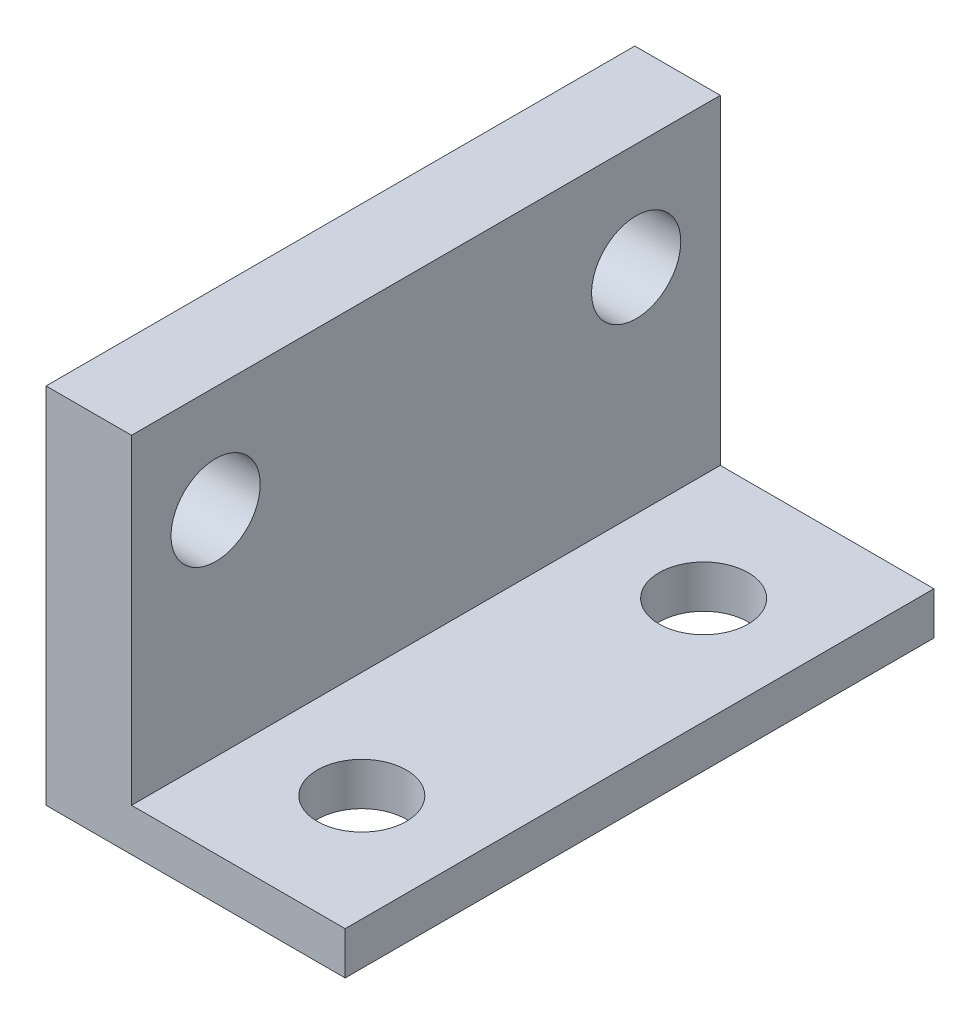
SolidWorks part; units mm, degrees
ref_plane "Front Plane" through (0, 0, 0) normal (0, 0, 1) x (1, 0, 0)
ref_plane "Top Plane" through (0, 0, 0) normal (0, 1, 0) x (1, 0, 0)
ref_plane "Right Plane" through (0, 0, 0) normal (1, 0, 0) x (0, 0, -1)
sketch "Sketch1" plane through (0, 0, 0) normal (0, 0, 1) x (1, 0, 0)
  line L1 (0, 0) -> (17.78, 0)
  line L2 (0, 0) -> (0, 2.54)
  line L3 (0, 2.54) -> (17.78, 2.54)
  line L4 (17.78, 0) -> (17.78, 2.54)
  line L5 (0, 2.54) -> (5.08, 2.54)
  line L6 (0, 2.54) -> (0, 21.59)
  line L7 (0, 21.59) -> (5.08, 21.59)
  line L8 (5.08, 2.54) -> (5.08, 21.59)
  dimension "D1" = 5.08
  dimension "D2" = 12.7
  dimension "D3" = 19.05
  dimension "D4" = 2.54
extrude "Boss-Extrude1" add sketch "Sketch1" along normal blind 35 contours L6 L5 L8 L7 | L2 L1 L4 L3
hole_wizard "Ø5.0mm Dowel Hole1" positions "Sketch2" profile "Sketch3" hole size "Ø5.0" standard "ANSI Metric" end condition through all
sketch "Sketch2" plane through (5.08, 0, 0) normal (1, 0, 0) x (0, 0, -1)
  line L4 (-30, 15.24) -> (-5, 15.24) construction
  line L6 (-35, 0) -> (0, 0) construction
  point P0 (-30, 15.24)
  point P2 (-5, 15.24)
  point P19 (-17.5, 0)
  point P20 (-17.5, 15.24)
  dimension "D1" = 25
  dimension "D2" = 15.24
sketch "Sketch3" plane through (5.08, 15.24, 30) normal (0, 1, 0) x (0, 0, -1)
  line L0 (0, 0) -> (0, 5.08)
  line L1 (0, 5.08) -> (2.65, 5.08)
  line L2 (2.65, 5.08) -> (2.65, 0)
  line L5 (2.65, 0) -> (0, 0)
  line L11 (0, -6.35) -> (0, 107.95) construction
  dimension "Thru Hole Dia." = 5.3
  dimension "Thru Hole Depth" = 5.08
hole_wizard "Ø5.0mm Dowel Hole2" positions "Sketch4" profile "Sketch5" hole size "Ø5.0" standard "ANSI Metric" end condition through all
sketch "Sketch4" plane through (0, 2.54, 0) normal (0, 1, 0) x (1, 0, 0)
  line L2 (11.43, -7.34) -> (11.43, -27.66) construction
  line L3 (17.78, -35) -> (17.78, 0) construction
  line L6 (0, -35) -> (0, 0) construction
  point P0 (11.43, -27.66)
  point P2 (11.43, -7.34)
  point P11 (11.3672, -27.38)
  point P12 (11.493, -7.06)
  point P16 (17.78, -17.5)
  point P17 (11.43, -17.5)
  dimension "D1" = 20.32
  dimension "D2" = 11.43
sketch "Sketch5" plane through (11.43, 2.54, 27.66) normal (1, 0, 0) x (0, 0, 1)
  line L0 (0, 0) -> (0, 2.54)
  line L1 (0, 2.54) -> (2.65, 2.54)
  line L2 (2.65, 2.54) -> (2.65, 0)
  line L5 (2.65, 0) -> (0, 0)
  line L11 (0, -6.35) -> (0, 107.95) construction
  dimension "Thru Hole Dia." = 5.3
  dimension "Thru Hole Depth" = 2.54
equation "\"wall thicc\"= 2.5mm"
equation "\"press fit\"= 0.3mm"
equation "\"shaft thick\"= 5mm + \"press fit\""
equation "\"D4@Sketch1\"=\"wall thicc\""
